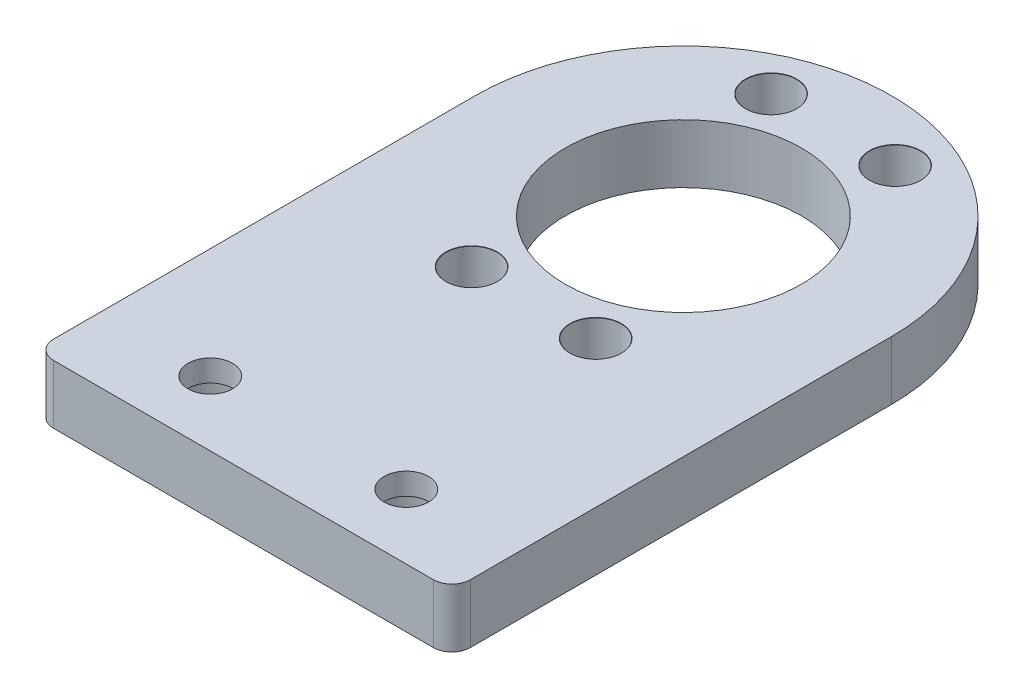
SolidWorks part; units mm, degrees
material "ABS PC"
ref_plane "Front Plane" through (0, 0, 0) normal (0, 0, 1) x (1, 0, 0)
ref_plane "Top Plane" through (0, 0, 0) normal (0, 1, 0) x (1, 0, 0)
ref_plane "Right Plane" through (0, 0, 0) normal (1, 0, 0) x (0, 0, -1)
sketch "Sketch1" plane through (0, 0, 0) normal (0, 1, 0) x (1, 0, 0)
  line L5 (-22.5, -47.5) -> (22.5, -47.5)
  line L6 (-22.5, -47.5) -> (-22.5, 0)
  line L8 (22.5, -47.5) -> (22.5, 0)
  line L9 (-22.5, -47.5) -> (22.5, 0) construction
  line L10 (-22.5, 0) -> (22.5, -47.5) construction
  arc A0 (22.5, 0) -> (-22.5, 0) centre (0, 0) ccw
  point P2 (0, -23.75)
  dimension "D1" = 45
  dimension "D2" = 70
  dimension "D3" = 45
extrude "Boss-Extrude1" add sketch "Sketch1" along normal blind 6.35
sketch "Sketch2" plane through (0, 6.35, 0) normal (0, 1, 0) x (1, 0, 0)
  line L0 (-6.697, 16.1679) -> (6.697, 16.1679) construction
  circle A0 centre (0, 0) radius 17.5 construction
  circle A1 centre (0, 0) radius 17.5 construction
  circle A2 centre (0, 0) radius 17.5 construction
  circle A3 centre (0, 0) radius 17.5 construction
  circle A4 centre (0, 0) radius 17.5 construction
  circle A5 centre (0, 0) radius 17.5 construction
  circle A6 centre (0, 0) radius 17.5 construction
  circle A7 centre (0, 0) radius 17.5 construction
  point P3 (-6.697, 16.1679)
  point P5 (-16.1679, -6.697)
  point P7 (6.697, 16.1679)
  point P9 (16.1679, 6.697)
  point P11 (16.1679, -6.697)
  point P13 (6.697, -16.1679)
  point P15 (-6.697, -16.1679)
  point P16 (0, 0)
  point P18 (-16.1679, 6.697)
  point P19 (0, 0)
  dimension "D1" = 35
  dimension "D2" = 8
hole_wizard "M5 Clearance Hole1" positions "Sketch3" profile "Sketch4" hole size "M5" standard "ANSI Metric" end condition through all
sketch "Sketch3" plane through (0, 6.35, 0) normal (0, 1, 0) x (1, 0, 0)
  point P0 (-6.697, -16.1679)
  point P3 (6.697, -16.1679)
  point P6 (6.697, 16.1679)
  point P15 (-6.697, 16.1679)
sketch "Sketch4" plane through (-6.697, 6.35, 16.1679) normal (1, 0, 0) x (0, 0, 1)
  line L0 (0, 0) -> (0, 6.35)
  line L1 (0, 6.35) -> (2.75, 6.35)
  line L2 (2.75, 6.35) -> (2.75, 0.025)
  line L3 (2.75, 0.025) -> (2.775, 0)
  line L5 (2.775, 0) -> (0, 0)
  line L6 (-2.75, 0.025) -> (-2.775, 0) construction
  line L11 (0, -6.35) -> (0, 107.95) construction
  dimension "Thru Hole Dia." = 5.5
  dimension "Thru Hole Depth" = 6.35
  dimension "Near C'Sink Dia." = 5.55
  dimension "Near C'Sink Angle" = 90
sketch "Sketch5" plane through (0, 6.35, 0) normal (0, 1, 0) x (1, 0, 0)
  circle A0 centre (0, 0) radius 12.75
  dimension "D1" = 25.5
extrude "Cut-Extrude1" cut sketch "Sketch5" against normal through all
sketch "Sketch6" [suppressed] plane through (0, 6.35, 0) normal (0, 1, 0) x (1, 0, 0)
  line L0 (-22.5, -77.5) -> (22.5, -77.5) construction
  circle A0 centre (0, -71) radius 3.3782
  dimension "D1" = 6.7564
  dimension "D2" = 6.5
sketch "Sketch7" [suppressed] plane through (0, 6.35, 0) normal (0, 1, 0) x (1, 0, 0)
  line L0 (12.5, -58.5) -> (-12.5, -58.5) construction
  line L1 (12.5, -63) -> (-12.5, -63)
  line L2 (12.5, -54) -> (-12.5, -54)
  line L3 (0, -71) -> (0, 0) construction
  line L4 (12.5, -42.5) -> (-12.5, -42.5) construction
  line L5 (12.5, -47) -> (-12.5, -47)
  line L6 (12.5, -38) -> (-12.5, -38)
  line L7 (12.5, -26.5) -> (-12.5, -26.5) construction
  line L8 (12.5, -31) -> (-12.5, -31)
  line L9 (12.5, -22) -> (-12.5, -22)
  arc A0 (12.5, -63) -> (12.5, -54) centre (12.5, -58.5) ccw
  arc A1 (-12.5, -54) -> (-12.5, -63) centre (-12.5, -58.5) ccw
  arc A2 (12.5, -47) -> (12.5, -38) centre (12.5, -42.5) ccw
  arc A3 (-12.5, -38) -> (-12.5, -47) centre (-12.5, -42.5) ccw
  arc A4 (12.5, -31) -> (12.5, -22) centre (12.5, -26.5) ccw
  arc A5 (-12.5, -22) -> (-12.5, -31) centre (-12.5, -26.5) ccw
  circle A6 centre (0, -71) radius 3.3782 construction
  point P2 (0, -58.5)
  point P15 (0, -42.5)
  point P22 (0, -26.5)
  point P28 (0, -63)
  dimension "D2" = 4.5
  dimension "D4" = 8
  dimension "D3" = 25
  dimension "D1" = 3
extrude "Cut-Extrude3" [suppressed] cut sketch "Sketch7" against normal through all
sketch "Sketch8" plane through (0, 0, 0) normal (0, -1, 0) x (1, 0, 0)
  line L0 (10.5848, 40.5) -> (-10.5848, 40.5) construction
  line L1 (-22.5, 47.5) -> (22.5, 47.5) construction
  point P2 (0, 40.5)
  point P5 (0, 47.5)
  dimension "D1" = 7
  dimension "D2" = 21.1696
hole_wizard "CBORE for M4 SHCS1" positions "Sketch9" profile "Sketch10" counterbore size "M4" standard "ANSI Metric" end condition through all
sketch "Sketch9" plane through (0, 0, 0) normal (0, -1, 0) x (-1, 0, 0)
  point P0 (-10.5848, -40.5)
  point P3 (10.5848, -40.5)
sketch "Sketch10" plane through (10.5848, 0, 40.5) normal (1, 0, 0) x (0, 0, -1)
  line L0 (0, 0) -> (0, 6.35)
  line L1 (0, 6.35) -> (2.4, 6.35)
  line L3 (2.4, 6.35) -> (2.4, 4)
  line L4 (4, 4) -> (2.4, 4)
  line L5 (4, 4) -> (4, 0.025)
  line L6 (4, 0.025) -> (4.025, 0)
  line L7 (4.025, 0) -> (0, 0)
  line L8 (-4, 0.025) -> (-4.025, 0) construction
  line L11 (0, -6.35) -> (0, 107.95) construction
  dimension "Thru Hole Dia." = 4.8
  dimension "Thru Hole Depth" = 6.35
  dimension "C'Bore Dia." = 8
  dimension "C'Bore Depth" = 4
  dimension "Near C'Sink Dia." = 8.05
  dimension "Near C'Sink Angle" = 90
fillet "Fillet1" radius 2 2 edges at (-22.5, 3.175, 47.5) (22.5, 3.175, 47.5)
